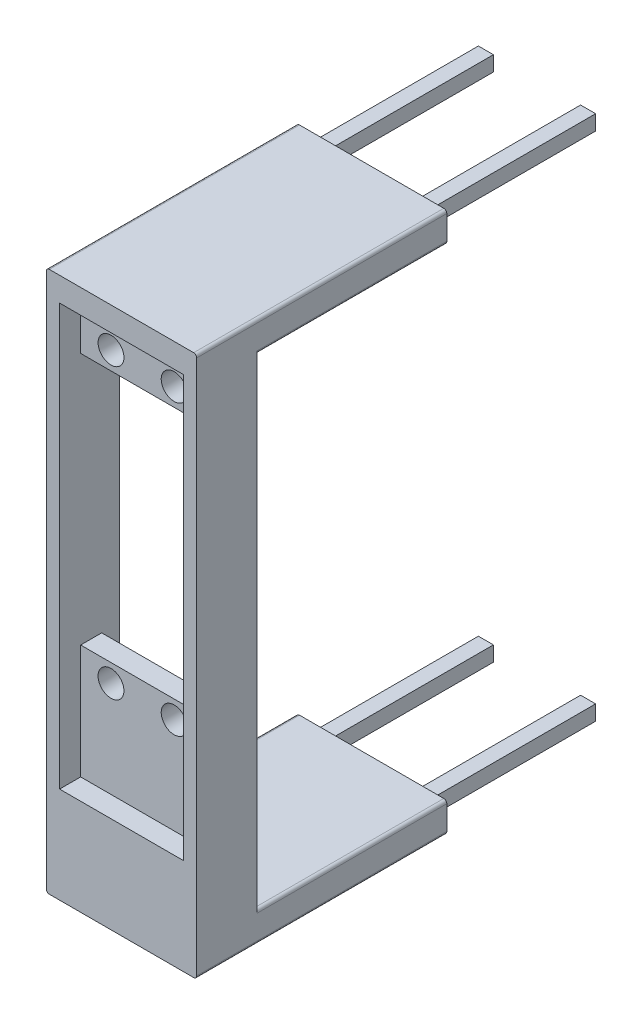
SolidWorks part; units mm, degrees
material "Custom Plastic"
ref_plane "Front Plane" through (0, 0, 0) normal (0, 0, 1) x (1, 0, 0)
ref_plane "Top Plane" through (0, 0, 0) normal (0, 1, 0) x (1, 0, 0)
ref_plane "Right Plane" through (0, 0, 0) normal (1, 0, 0) x (0, 0, -1)
sketch "Sketch2" plane through (0, 0, -60.1331) normal (0, 0, 1) x (1, 0, 0)
  line L0 (165.5709, -7.7744) -> (110.5709, -7.7744) construction
  line L5 (113.0709, -2.7744) -> (138.0709, -2.7744)
  line L6 (113.0709, -2.7744) -> (113.0709, -7.7744)
  line L7 (113.0709, -7.7744) -> (138.0709, -7.7744)
  line L8 (138.0709, -2.7744) -> (138.0709, -7.7744)
  line L9 (110.5709, -2.7744) -> (160.5709, -2.7744) construction
  line L10 (165.5709, 82.2256) -> (110.5709, 82.2256) construction
  line L11 (113.0709, 82.2256) -> (138.0709, 82.2256)
  line L12 (113.0709, 82.2256) -> (113.0709, 77.2256)
  line L13 (113.0709, 77.2256) -> (138.0709, 77.2256)
  line L14 (138.0709, 82.2256) -> (138.0709, 77.2256)
  line L17 (115.5709, -5.2744) -> (113.0709, -5.2744)
  line L18 (115.5709, -3.7744) -> (115.5709, -6.7744) construction
  line L19 (135.5709, -5.2744) -> (138.0709, -5.2744)
  line L20 (160.5709, 77.2256) -> (110.5709, 77.2256) construction
  line L21 (135.5709, -3.7744) -> (135.5709, -6.7744) construction
  line M13 (165.5709, 82.2256) -> (110.5709, 82.2256)
  line M15 (110.5709, 77.2256) -> (160.5709, 77.2256)
  line M19 (160.5709, -2.7744) -> (110.5709, -2.7744)
  line M21 (110.5709, -7.7744) -> (165.5709, -7.7744)
  line M23 (115.5709, -3.7744) -> (118.5709, -3.7744)
  line M24 (118.5709, -3.7744) -> (118.5709, -6.7744)
  line M25 (118.5709, -6.7744) -> (115.5709, -6.7744)
  line M26 (115.5709, -6.7744) -> (115.5709, -3.7744)
  line M27 (132.5709, 81.2256) -> (135.5709, 81.2256)
  line M28 (135.5709, 81.2256) -> (135.5709, 78.2256)
  line M29 (135.5709, 78.2256) -> (132.5709, 78.2256)
  line M30 (132.5709, 78.2256) -> (132.5709, 81.2256)
  line M31 (115.5709, 81.2256) -> (118.5709, 81.2256)
  line M32 (118.5709, 81.2256) -> (118.5709, 78.2256)
  line M33 (118.5709, 78.2256) -> (115.5709, 78.2256)
  line M34 (115.5709, 78.2256) -> (115.5709, 81.2256)
  line M35 (132.5709, -3.7744) -> (135.5709, -3.7744)
  line M36 (135.5709, -3.7744) -> (135.5709, -6.7744)
  line M37 (135.5709, -6.7744) -> (132.5709, -6.7744)
  line M38 (132.5709, -6.7744) -> (132.5709, -3.7744)
  dimension "D1" = 25
extrude "Boss-Extrude1" add sketch "Sketch2" along normal up to surface (31.5956 mm away) contours L8 L6 M38 M35 M36 M19 M26 M23 M24 M25 M21 M37 | L14 L12 M13 M15 M34 M31 M32 M33 M30 M27 M28 M29 region at (125.5709, -5.2744, -60.1331) region at (125.5709, 79.7256, -60.1331)
sketch "Sketch3" plane through (0, 0, -60.1331) normal (0, 0, 1) x (1, 0, 0)
  line L0 (165.5709, -7.7744) -> (110.5709, -7.7744) construction
  line L1 (113.0709, 82.2256) -> (138.0709, 82.2256)
  line L2 (113.0709, 82.2256) -> (113.0709, -7.7744)
  line L3 (113.0709, -7.7744) -> (138.0709, -7.7744)
  line L4 (138.0709, 82.2256) -> (138.0709, -7.7744)
sketch "Sketch4" plane through (0, 0, -28.5375) normal (0, 0, 1) x (1, 0, 0)
  line L1 (113.0709, 82.2256) -> (138.0709, 82.2256)
  line L2 (113.0709, 82.2256) -> (113.0709, -7.7744)
  line L3 (113.0709, -7.7744) -> (138.0709, -7.7744)
  line L4 (138.0709, 82.2256) -> (138.0709, -7.7744)
extrude "Boss-Extrude3" add sketch "Sketch4" along normal blind 10
sketch "Sketch6" plane through (0, 0, -18.5375) normal (0, 0, 1) x (1, 0, 0)
  line L0 (113.0709, 82.2256) -> (138.0709, 82.2256) construction
  line L2 (113.0709, 82.2256) -> (113.0709, -7.7744) construction
  line L3 (138.0709, 82.2256) -> (138.0709, -7.7744) construction
  circle A2 centre (120.3209, 72.2256) radius 2.15
  circle A3 centre (130.8209, 72.2256) radius 2.15
  circle A4 centre (130.8209, 24.2256) radius 2.15
  circle A5 centre (120.3209, 24.2256) radius 2.15
  circle A6 centre (130.8209, 72.2256) radius 2.15
  dimension "D1" = 4.3
  dimension "D2" = 10
  dimension "D3" = 7.25
  dimension "D4" = 10.5
  dimension "D5" = 48
  dimension "D6" = 48
  dimension "D7" = 10.5
  dimension "D8" = 7.25
extrude "Cut-Extrude2" cut sketch "Sketch6" against normal blind 10 contours A4 | A5 | A6 | A2 region at (120.3209, 72.2256, -18.5375) region at (130.8209, 72.2256, -18.5375) region at (130.8209, 24.2256, -18.5375) region at (120.3209, 24.2256, -18.5375)
sketch "Sketch7" plane through (0, 0, -18.5375) normal (0, 0, 1) x (1, 0, 0)
  line L5 (120.3209, 24.2256) -> (120.3209, 27.2256) construction
  line L6 (135.8709, 69.2256) -> (135.8709, 27.2256)
  line L7 (115.2709, 69.2256) -> (135.8709, 69.2256)
  line L9 (115.2709, 27.2256) -> (135.8709, 27.2256)
  line L11 (115.2709, 69.2256) -> (115.2709, 27.2256)
  line L12 (138.0709, -2.7744) -> (138.0709, 77.2256) construction
  line L13 (120.3209, 72.2256) -> (120.3209, 69.2256) construction
  dimension "D1" = 20.6
  dimension "D2" = 42
  dimension "D3" = 2.2
extrude "Cut-Extrude3" cut sketch "Sketch7" against normal blind 10
sketch "Sketch8" plane through (0, 0, -60.1331) normal (0, 0, -1) x (-1, 0, 0)
  line L0 (-135.5709, -3.7744) -> (-135.5709, -6.7744) construction
  line L1 (-135.5709, 81.2256) -> (-132.5709, 81.2256)
  line L2 (-135.5709, 81.2256) -> (-135.5709, 78.2256)
  line L3 (-135.5709, 78.2256) -> (-132.5709, 78.2256)
  line L4 (-132.5709, 81.2256) -> (-132.5709, 78.2256)
  line L5 (-118.5709, 81.2256) -> (-115.5709, 81.2256)
  line L6 (-118.5709, 81.2256) -> (-118.5709, 78.2256)
  line L7 (-118.5709, 78.2256) -> (-115.5709, 78.2256)
  line L8 (-115.5709, 81.2256) -> (-115.5709, 78.2256)
  line L9 (-135.5709, -3.7744) -> (-132.5709, -3.7744)
  line L10 (-135.5709, -3.7744) -> (-135.5709, -6.7744)
  line L11 (-135.5709, -6.7744) -> (-132.5709, -6.7744)
  line L12 (-132.5709, -3.7744) -> (-132.5709, -6.7744)
  line L13 (-135.3209, 80.9756) -> (-132.8209, 78.4756)
  line L14 (-115.5709, -6.7744) -> (-118.5709, -6.7744)
  line L15 (-115.5709, -6.7744) -> (-115.5709, -3.7744)
  line L16 (-115.5709, -3.7744) -> (-118.5709, -3.7744)
  line L17 (-118.5709, -6.7744) -> (-118.5709, -3.7744)
  line L18 (-135.3209, 80.9756) -> (-132.8209, 80.9756)
  line L19 (-135.3209, 80.9756) -> (-135.3209, 78.4756)
  line L20 (-135.3209, 78.4756) -> (-132.8209, 78.4756)
  line L21 (-132.8209, 80.9756) -> (-132.8209, 78.4756)
  line L22 (-135.5709, 81.2256) -> (-132.5709, 78.2256)
  line L23 (-118.5709, 81.2256) -> (-115.5709, 78.2256) construction
  line L24 (-118.3209, 80.9756) -> (-115.8209, 80.9756)
  line L25 (-118.3209, 80.9756) -> (-118.3209, 78.4756)
  line L26 (-118.3209, 78.4756) -> (-115.8209, 78.4756)
  line L27 (-115.8209, 80.9756) -> (-115.8209, 78.4756)
  line L28 (-118.3209, 78.4756) -> (-115.8209, 80.9756)
  line L29 (-135.5709, -3.7744) -> (-132.5709, -6.7744) construction
  line L30 (-135.3209, -4.0244) -> (-132.8209, -4.0244)
  line L31 (-135.3209, -4.0244) -> (-135.3209, -6.5244)
  line L32 (-135.3209, -6.5244) -> (-132.8209, -6.5244)
  line L33 (-132.8209, -4.0244) -> (-132.8209, -6.5244)
  line L34 (-135.3209, -4.0244) -> (-132.8209, -6.5244) construction
  line L35 (-118.3209, -4.0244) -> (-115.8209, -6.5244) construction
  line L36 (-118.3209, -4.0244) -> (-115.8209, -4.0244)
  line L37 (-118.3209, -4.0244) -> (-118.3209, -6.5244)
  line L38 (-118.3209, -6.5244) -> (-115.8209, -6.5244)
  line L39 (-115.8209, -4.0244) -> (-115.8209, -6.5244)
  line L40 (-118.5709, -3.7744) -> (-115.5709, -6.7744) construction
  point P29 (-134.0709, 79.7256)
  point P30 (-134.0709, 79.7256)
  point P35 (-117.0709, 79.7256)
  point P36 (-117.0709, 79.7256)
  point P41 (-134.0709, -5.2744)
  point P42 (-134.0709, -5.2744)
  point P47 (-117.0709, -5.2744)
  point P48 (-117.0709, -5.2744)
  dimension "D1" = 2.5
  dimension "D2" = 2.5
  dimension "D3" = 2.5
  dimension "D4" = 2.5
sketch "Sketch9" plane through (138.0709, 0, 0) normal (1, 0, 0) x (0, 0, -1)
  line L0 (18.5375, 82.2256) -> (60.1331, 82.2256) construction
  line L1 (60.1331, -7.7744) -> (58.1331, -7.7744)
  line L2 (60.1331, -7.7744) -> (60.1331, 82.2256)
  line L3 (60.1331, 82.2256) -> (58.1331, 82.2256)
  line L4 (58.1331, -7.7744) -> (58.1331, 82.2256)
  dimension "D1" = 2
extrude "Cut-Extrude4" cut sketch "Sketch9" against normal through all
sketch "Sketch10" plane through (138.0709, 0, 0) normal (1, 0, 0) x (0, 0, -1)
  line L1 (58.1331, 82.2256) -> (60.1331, 82.2256)
  line L2 (58.1331, 82.2256) -> (58.1331, -7.7744)
  line L3 (58.1331, -7.7744) -> (60.1331, -7.7744)
  line L4 (60.1331, 82.2256) -> (60.1331, -7.7744)
  dimension "D1" = 2
extrude "Boss-Extrude4" add sketch "Sketch10" against normal up to surface (25 mm away) up to face at (113.0709, 37.2256, -40.8353)
extrude "Boss-Extrude5" add sketch "Sketch8" along normal blind 27.5 contours L19 L20 L13 | L21 L18 L13 | L25 L28 L24 | L28 L26 L27 | L39 L36 L37 L38 | L33 L30 L31 L32 region at (133.6542, 80.1423, -60.1331) region at (134.4876, 79.309, -60.1331) region at (117.4876, 80.1423, -60.1331) region at (116.6542, 79.309, -60.1331) region at (134.0709, -5.2744, -60.1331) region at (117.0709, -5.2744, -60.1331)
sketch "Sketch11" plane through (138.0709, 0, 0) normal (1, 0, 0) x (0, 0, -1)
  line L1 (58.1331, 77.2256) -> (61.1331, 77.2256)
  line L2 (58.1331, 77.2256) -> (58.1331, -2.7744)
  line L3 (58.1331, -2.7744) -> (61.1331, -2.7744)
  line L4 (61.1331, 77.2256) -> (61.1331, -2.7744)
  dimension "D1" = 3
extrude "Cut-Extrude5" cut sketch "Sketch11" against normal through all
sketch "Sketch13" plane through (0, 0, -28.5375) normal (0, 0, -1) x (-1, 0, 0)
  line L1 (-135.8709, 75.4756) -> (-115.2709, 75.4756)
  line L2 (-135.8709, 75.4756) -> (-135.8709, 18.4756)
  line L3 (-135.8709, 18.4756) -> (-115.2709, 18.4756)
  line L4 (-115.2709, 75.4756) -> (-115.2709, 18.4756)
  line L8 (-135.8709, 69.2256) -> (-115.2709, 69.2256) construction
  line L9 (-115.2709, 27.2256) -> (-135.8709, 27.2256) construction
  line L10 (-135.8709, 27.2256) -> (-135.8709, 69.2256) construction
  dimension "D1" = 6.25
  dimension "D2" = 8.75
  dimension "D3" = 20.6
extrude "Cut-Extrude6" cut sketch "Sketch13" against normal blind 3
fillet "Fillet1" radius 0.5 8 edges at (138.0709, 82.2256, -39.3353) (138.0709, -7.7744, -39.3353) (113.0709, -7.7744, -39.3353) (113.0709, 82.2256, -39.3353) (113.0709, 77.2256, -44.3353) (113.0709, -2.7744, -44.3353) (138.0709, 77.2256, -44.3353) (138.0709, -2.7744, -44.3353)
sketch "Sketch14" plane through (0, 0, -18.5375) normal (0, 0, 1) x (1, 0, 0)
  line L0 (137.5709, 82.2256) -> (113.5709, 82.2256) construction
  line L1 (115.2709, 78.2256) -> (135.8709, 78.2256)
  line L2 (115.2709, 78.2256) -> (115.2709, 8.2256)
  line L3 (115.2709, 8.2256) -> (135.8709, 8.2256)
  line L4 (135.8709, 78.2256) -> (135.8709, 8.2256)
  line L5 (113.0709, 81.7256) -> (113.0709, -7.2744) construction
  dimension "D1" = 70
  dimension "D2" = 20.6
  dimension "D3" = 4
  dimension "D4" = 2.2
extrude "Cut-Extrude7" cut sketch "Sketch14" against normal blind 3.5
